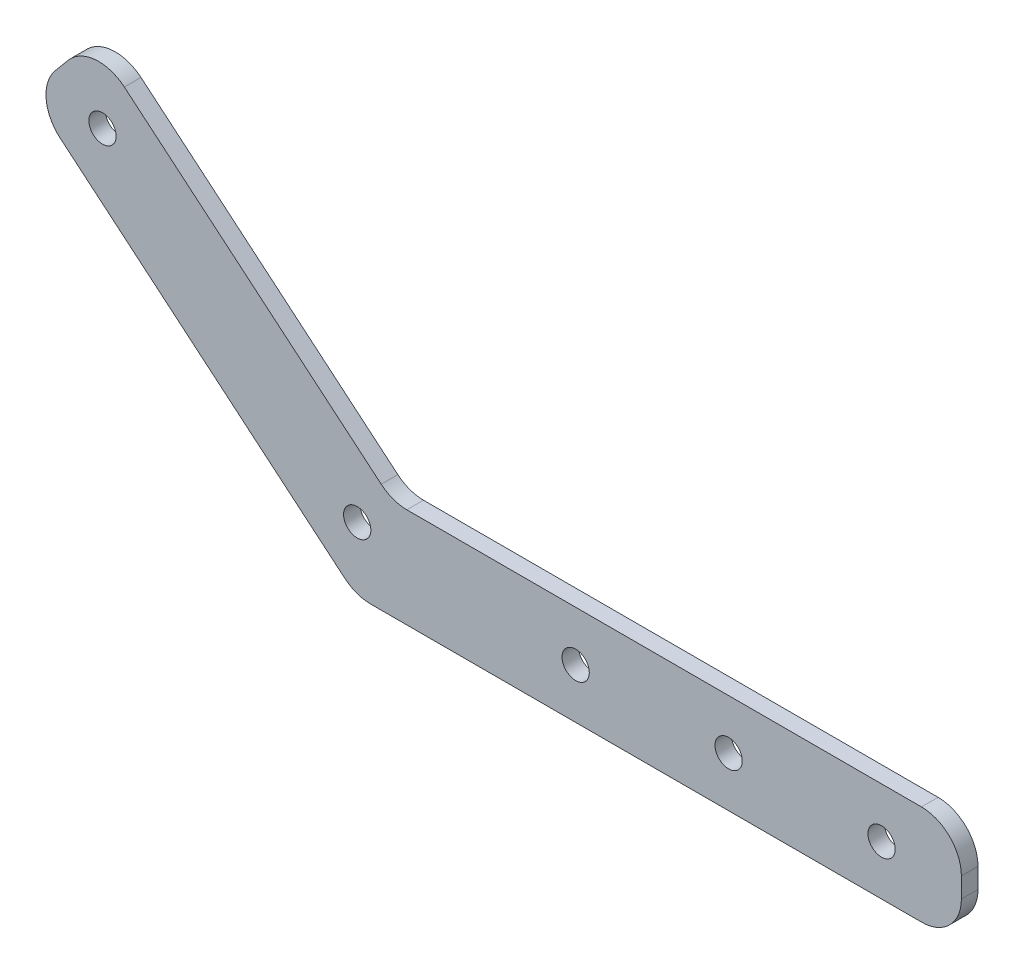
SolidWorks part; units mm, degrees
ref_plane "Front Plane" through (0, 0, 0) normal (0, 0, 1) x (1, 0, 0)
ref_plane "Top Plane" through (0, 0, 0) normal (0, 1, 0) x (1, 0, 0)
ref_plane "Right Plane" through (0, 0, 0) normal (1, 0, 0) x (0, 0, -1)
sketch "Sketch2" plane through (0, 0, 0) normal (0, 0, 1) x (1, 0, 0)
  line L4 (-73.66, 0) -> (0, 0) construction
  line L5 (0, -9.525) -> (0, 9.525)
  line L6 (0, 9.525) -> (-108.6696, 9.525)
  line L7 (-108.6696, 9.525) -> (-165.6824, 57.3644)
  line L8 (-165.6824, 57.3644) -> (-177.9275, 42.7713)
  line L9 (-177.9275, 42.7713) -> (-115.6032, -9.525)
  line L10 (-115.6032, -9.525) -> (0, -9.525)
  line L11 (-171.8049, 50.0678) -> (-100.7849, -9.525) construction
  line L12 (-164.0219, 43.5371) -> (-115.3781, 2.7201) construction
  circle A10 centre (-164.0219, 43.5371) radius 2.6035
  circle A11 centre (-115.3781, 2.7201) radius 2.6035
  circle A12 centre (-139.7, 23.1286) radius 14.2875 construction
  circle A13 centre (-73.66, 0) radius 2.6035
  circle A14 centre (-44.45, 0) radius 2.6035
  circle A15 centre (-15.24, 0) radius 2.6035
  point P4 (0, 0)
  point P26 (-139.7, 23.1286)
  dimension "D11" = 28.575
  dimension "D2" = 5.207
  dimension "D7" = 63.5
  dimension "D8" = 10.16
  dimension "D9" = 19.05
  dimension "D10" = 19.05
  dimension "D12" = 139.7
  dimension "D13" = 140
  dimension "D14" = 19.05
  dimension "D3" = 29.21
  dimension "D5" = 29.21
  dimension "D6" = 15.24
extrude "Boss-Extrude1" add sketch "Sketch2" along normal blind 3.175
sketch "Sketch3" [suppressed] plane through (0, 0, 0) normal (0, 0, 1) x (1, 0, 0)
  line L0 (-116.5911, -10.16) -> (0, -10.16) construction
  line L1 (0, 10.16) -> (-109.1952, 10.16)
  line L2 (0, 10.16) -> (0, -10.16)
  line L3 (0, -10.16) -> (-109.1952, -10.16)
  line L4 (-109.1952, 10.16) -> (-109.1952, -10.16)
extrude "Boss-Extrude2" [suppressed] add sketch "Sketch3" along normal up to surface (3.175 mm away) from surface
sketch "Sketch4" [suppressed] plane through (0, 0, 0) normal (0, 0, 1) x (1, 0, 0)
  line L0 (-86.36, 0) -> (-27.94, 0) construction
  line L1 (-116.5911, -10.16) -> (0, -10.16) construction
  line L2 (0, 10.16) -> (-12.7, 10.16)
  line L3 (0, 10.16) -> (0, -10.16)
  line L4 (0, -10.16) -> (-12.7, -10.16)
  line L5 (-12.7, 10.16) -> (-12.7, -10.16)
  circle A0 centre (-27.94, 0) radius 2.6035
  circle A1 centre (-86.36, 0) radius 2.6035
  circle A2 centre (-57.15, 0) radius 2.6035
  circle A18 centre (-15.24, 0) radius 2.6035 construction
  dimension "D1" = 12.7
  dimension "D3" = 12.7
extrude "Cut-Extrude5" [suppressed] cut sketch "Sketch4" against normal through all and the other way through all contours A0 | L2 L5 L4 L3 | L0 A2 | A2 L0 | A1 | A1
fillet "Fillet1" radius 7.62 6 edges at (-177.9275, 42.7713, 1.5875) (-115.6032, -9.525, 1.5875) (0, -9.525, 1.5875) (0, 9.525, 1.5875) (-108.6696, 9.525, 1.5875) (-165.6824, 57.3644, 1.5875)
fillet "Fillet2" [suppressed] radius 7.62
equation "\"D5@Sketch2\"=\"D3@Sketch2\""
equation "\"D2@Sketch4\"=\"D1@Sketch4\""
equation "\"D3@Sketch4\"=\"D1@Sketch4\""
